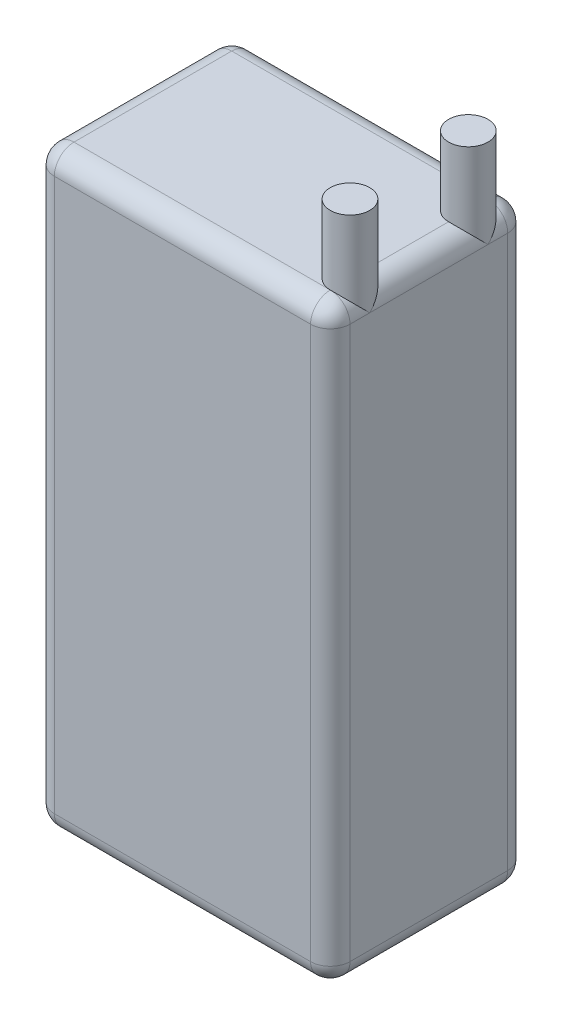
SolidWorks part; units mm, degrees
ref_plane "Front Plane" through (0, 0, 0) normal (0, 0, 1) x (1, 0, 0)
ref_plane "Top Plane" through (0, 0, 0) normal (0, 1, 0) x (1, 0, 0)
ref_plane "Right Plane" through (0, 0, 0) normal (1, 0, 0) x (0, 0, -1)
sketch "Sketch1" plane through (0, 0, 0) normal (0, 1, 0) x (1, 0, 0)
  line L1 (15, 10) -> (-15, 10)
  line L2 (15, 10) -> (15, -10)
  line L3 (15, -10) -> (-15, -10)
  line L4 (-15, 10) -> (-15, -10)
  line L5 (15, 10) -> (-15, -10) construction
  line L6 (15, -10) -> (-15, 10) construction
  point P0 (0, 0)
  dimension "D1" = 30
  dimension "D2" = 20
extrude "Boss-Extrude1" add sketch "Sketch1" along normal blind 60
sketch "Sketch2" plane through (0, 60, 0) normal (0, 1, 0) x (1, 0, 0)
  line L4 (0, 0) -> (0, 5.1914) construction
  circle A2 centre (13, 6) radius 2
  circle A3 centre (13, -6) radius 2
extrude "Boss-Extrude2" add sketch "Sketch2" along normal blind 7
fillet "Fillet1" radius 2 14 edges at (15, 60, 8) (15, 60, -8) (0, 0, 10) (15, 0, 0) (0, 0, -10) (-15, 0, 0) (-15, 30, 10) (15, 30, 10) (-15, 60, 0) (0, 60, 10) (15, 60, 0) (15, 30, -10) (0, 60, -10) (-15, 30, -10)
